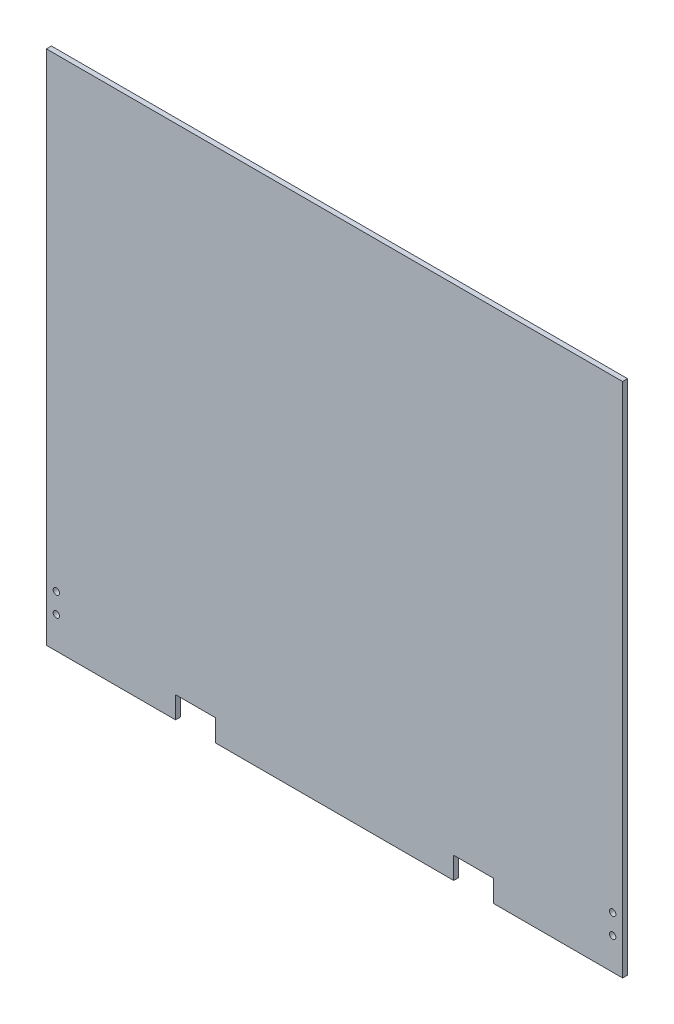
SolidWorks part; units mm, degrees
ref_plane "Front Plane" through (0, 0, 0) normal (0, 0, 1) x (1, 0, 0)
ref_plane "Top Plane" through (0, 0, 0) normal (0, 1, 0) x (1, 0, 0)
ref_plane "Right Plane" through (0, 0, 0) normal (1, 0, 0) x (0, 0, -1)
sketch "Sketch1" plane through (0, 0, 0) normal (0, 0, 1) x (1, 0, 0)
  line L0 (82.55, 0) -> (82.55, 13.97)
  line L1 (0, 0) -> (82.55, 0)
  line L2 (0, 0) -> (0, 330.2)
  line L3 (0, 330.2) -> (368.3, 330.2)
  line L4 (368.3, 0) -> (368.3, 330.2)
  line L5 (82.55, 13.97) -> (107.95, 13.97)
  line L6 (107.95, 13.97) -> (107.95, 0)
  line L7 (107.95, 0) -> (260.35, 0)
  line L8 (260.35, 0) -> (260.35, 13.97)
  line L9 (260.35, 13.97) -> (285.75, 13.97)
  line L10 (285.75, 13.97) -> (285.75, 0)
  line L11 (285.75, 0) -> (368.3, 0)
  line L12 (361.95, 33.02) -> (368.3, 33.02) construction
  line L13 (0, 20.32) -> (6.35, 20.32) construction
  circle A0 centre (6.35, 20.32) radius 2.032
  circle A1 centre (6.35, 33.02) radius 2.032
  circle A2 centre (361.95, 20.32) radius 2.032
  circle A3 centre (361.95, 33.02) radius 2.032
  dimension "D6" = 4.064
  dimension "D1" = 330.2
  dimension "D2" = 368.3
  dimension "D3" = 13.97
  dimension "D4" = 25.4
  dimension "D5" = 152.4
  dimension "D7" = 12.7
  dimension "D8" = 6.35
  dimension "D9" = 20.32
extrude "Boss-Extrude1" add sketch "Sketch1" along normal blind 3.175
